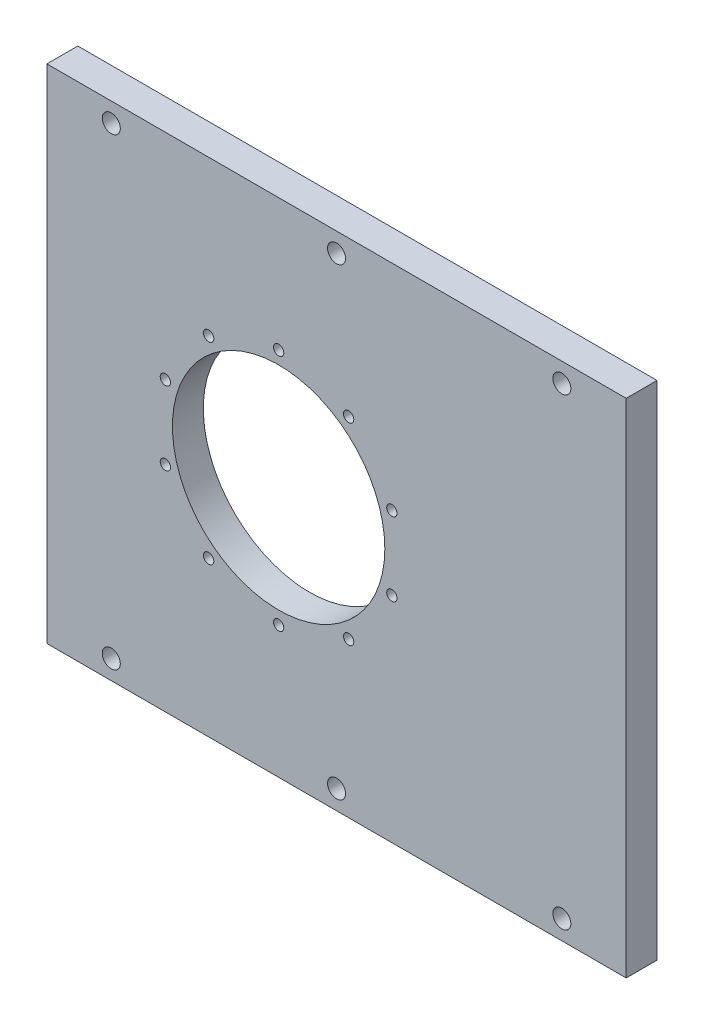
SolidWorks part; units mm, degrees
ref_plane "前视基准面" through (0, 0, 0) normal (0, 0, 1) x (1, 0, 0)
ref_plane "上视基准面" through (0, 0, 0) normal (0, 1, 0) x (1, 0, 0)
ref_plane "右视基准面" through (0, 0, 0) normal (1, 0, 0) x (0, 0, -1)
other "Configuration Table"
sketch "草图1" plane through (0, 0, 0) normal (0, 0, 1) x (1, 0, 0)
  line L0 (-225, 0) -> (225, 0) construction
  line L1 (-225, 195) -> (225, 195)
  line L2 (-225, 195) -> (-225, -195)
  line L3 (-225, -195) -> (225, -195)
  line L4 (225, 195) -> (225, -195)
  line L5 (-225, 195) -> (225, -195) construction
  line L6 (-225, -195) -> (225, 195) construction
  line L7 (0, 195) -> (0, -195) construction
  circle A0 centre (-45, 0) radius 82.5
  circle A1 centre (-45, 0) radius 92.5 construction
  circle A2 centre (-45, 92.5) radius 4
  circle A3 centre (9.3701, 74.8341) radius 4
  circle A4 centre (42.9727, 28.5841) radius 4
  circle A5 centre (42.9727, -28.5841) radius 4
  circle A6 centre (9.3701, -74.8341) radius 4
  circle A7 centre (-45, -92.5) radius 4
  circle A8 centre (-99.3701, -74.8341) radius 4
  circle A9 centre (-132.9727, -28.5841) radius 4
  circle A10 centre (-132.9727, 28.5841) radius 4
  circle A11 centre (-99.3701, 74.8341) radius 4
  circle A12 centre (0, 180) radius 7
  circle A13 centre (-175, 180) radius 7
  circle A14 centre (175, 180) radius 7
  circle A15 centre (-175, -180) radius 7
  circle A16 centre (0, -180) radius 7
  circle A17 centre (175, -180) radius 7
  point P0 (0, 0)
  point P33 (-45, 0)
  point P40 (0, 0)
  point P41 (0, 0)
  point P42 (0, 0)
  point P43 (0, 176.2924)
  dimension "D4" = 165
  dimension "D5" = 185
  dimension "D6" = 8
  dimension "D8" = 14
  dimension "D1" = 450
  dimension "D2" = 390
  dimension "D3" = 180
  dimension "D9" = 350
  dimension "D10" = 360
  dimension "D7" = 10
extrude "凸台-拉伸1" add sketch "草图1" along normal blind 24 contours L4 L3 L2 L1 | A0
extrude "切除-拉伸1" cut sketch "草图1<3>" against normal blind 18 from surface contours A13 | A12 | A14 | A10 | A11 | A2 | A3 | A4 | A5 | A6 | A7 | A8 | A9 | A15 | A16 | A17 starting at face at (0, 0, 24)
sketch "草图1<3>" plane through (0, 0, 0) normal (0, 0, 1) x (1, 0, 0) same geometry as "草图1"
